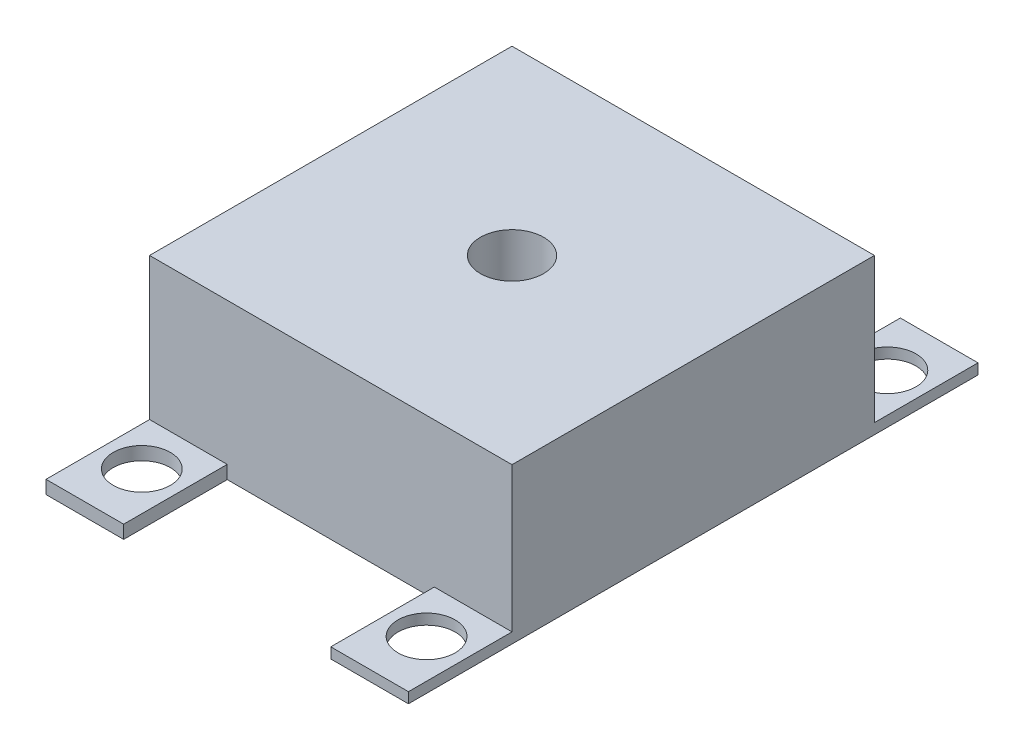
SolidWorks part; units mm, degrees
ref_plane "Front Plane" through (0, 0, 0) normal (0, 0, 1) x (1, 0, 0)
ref_plane "Top Plane" through (0, 0, 0) normal (0, 1, 0) x (1, 0, 0)
ref_plane "Right Plane" through (0, 0, 0) normal (1, 0, 0) x (0, 0, -1)
sketch "Sketch2" plane through (0, 0, 0) normal (0, 1, 0) x (1, 0, 0)
  line L1 (-17.5, 17.5) -> (17.5, 17.5)
  line L2 (-17.5, 17.5) -> (-17.5, -17.5)
  line L3 (-17.5, -17.5) -> (17.5, -17.5)
  line L4 (17.5, 17.5) -> (17.5, -17.5)
  line L5 (-17.5, 17.5) -> (17.5, -17.5) construction
  line L6 (-17.5, -17.5) -> (17.5, 17.5) construction
  point P0 (0, 0)
  dimension "D1" = 35
  dimension "D2" = 35
extrude "Boss-Extrude1" add sketch "Sketch2" along normal blind 10 contours L2 L1 L4 L3
sketch "Sketch3" plane through (0, 10, 0) normal (0, 1, 0) x (1, 0, 0)
  line L1 (-17.5, 17.5) -> (17.5, 17.5)
  line L2 (-17.5, 17.5) -> (-17.5, -17.5)
  line L3 (-17.5, -17.5) -> (17.5, -17.5)
  line L4 (17.5, 17.5) -> (17.5, -17.5)
  line L5 (-17.5, 17.5) -> (17.5, -17.5) construction
  line L6 (-17.5, -17.5) -> (17.5, 17.5) construction
  line L7 (-15, 15) -> (15, 15)
  line L8 (-15, 15) -> (-15, -15)
  line L9 (-15, -15) -> (15, -15)
  line L10 (15, 15) -> (15, -15)
  line L11 (-15, 15) -> (15, -15) construction
  line L12 (-15, -15) -> (15, 15) construction
  point P0 (0, 0)
  point P7 (0, 0)
  dimension "D1" = 30
extrude "Boss-Extrude2" add sketch "Sketch3" along normal blind 15 separate body
sketch "Sketch4" plane through (0, 25, 0) normal (0, 1, 0) x (1, 0, 0)
  line L1 (-17.5, 17.5) -> (17.5, 17.5)
  line L2 (-17.5, 17.5) -> (-17.5, -17.5)
  line L3 (-17.5, -17.5) -> (17.5, -17.5)
  line L4 (17.5, 17.5) -> (17.5, -17.5)
  line L5 (-17.5, 17.5) -> (17.5, -17.5) construction
  line L6 (-17.5, -17.5) -> (17.5, 17.5) construction
  point P0 (0, 0)
extrude "Boss-Extrude3" add sketch "Sketch4" along normal blind 15 separate body
sketch "Sketch5" plane through (0, 40, 0) normal (0, 1, 0) x (1, 0, 0)
  circle A0 centre (0, 0) radius 3.05
extrude "Cut-Extrude1" cut sketch "Sketch5" against normal up to surface (40 mm away) up to face at (0, 0, 0)
delete or keep bodies "Body-Delete/Keep 2" type delete bodies bodies 102 104
sketch "Sketch6" plane through (0, 0, -17.5) normal (0, 0, -1) x (-1, 0, 0)
  line L1 (-17.5, 25) -> (-10, 25)
  line L2 (-17.5, 25) -> (-17.5, 26.0178)
  line L3 (-17.5, 26.0178) -> (-10, 26.0178)
  line L4 (-10, 25) -> (-10, 26.0178)
  line L5 (17.5, 25) -> (10, 25)
  line L6 (17.5, 25) -> (17.5, 26.2762)
  line L7 (17.5, 26.2762) -> (10, 26.2762)
  line L8 (10, 25) -> (10, 26.2762)
  dimension "D1" = 7.5
  dimension "D2" = 7.5
extrude "Boss-Extrude4" add sketch "Sketch6" along normal blind 10 and the other way blind 45
sketch "Sketch7" plane through (0, 26.2762, 0) normal (0, 1, 0) x (1, 0, 0)
  line L0 (-17.5, 22.5) -> (-10, 22.5) construction
  line L1 (-17.5, 17.5) -> (-17.5, 27.5) construction
  line L2 (-10, 17.5) -> (-10, 27.5) construction
  circle A0 centre (-13.75, 22.5) radius 2.76
  circle A4 centre (13.75, 22.5) radius 2.76
  circle A5 centre (13.75, -22) radius 2.76
  circle A6 centre (-13.75, -22) radius 2.76
  dimension "D1" = 5.52
  dimension "D2" = 2
  dimension "D3" = 2
extrude "Cut-Extrude2" cut sketch "Sketch7" against normal blind 10 contours A0 | A5 | A4 | A6
